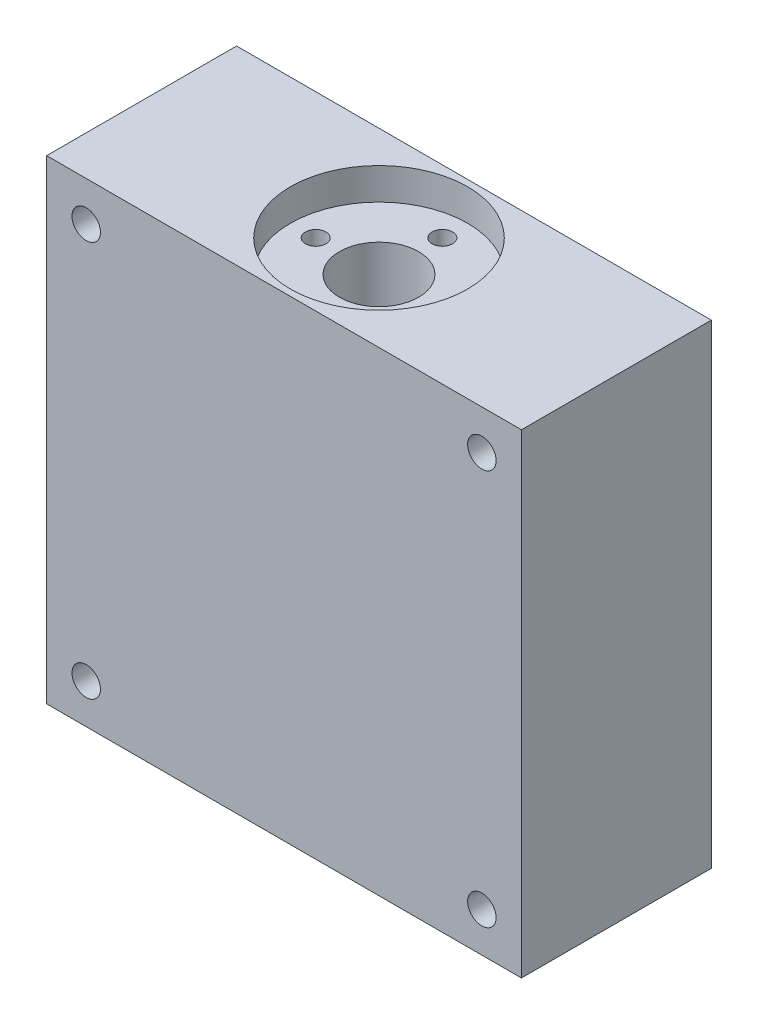
SolidWorks part; units mm, degrees
ref_plane "Front Plane" through (0, 0, 0) normal (0, 0, 1) x (1, 0, 0)
ref_plane "Top Plane" through (0, 0, 0) normal (0, 1, 0) x (1, 0, 0)
ref_plane "Right Plane" through (0, 0, 0) normal (1, 0, 0) x (0, 0, -1)
sketch "Sketch1" plane through (0, 0, 0) normal (0, 0, 1) x (1, 0, 0)
  line L1 (-30, 30) -> (30, 30)
  line L2 (-30, 30) -> (-30, -30)
  line L3 (-30, -30) -> (30, -30)
  line L4 (30, 30) -> (30, -30)
  line L5 (-30, 30) -> (30, -30) construction
  line L6 (-30, -30) -> (30, 30) construction
  line L7 (-25, -25) -> (25, -25) construction
  line L8 (-25, -25) -> (-25, 25) construction
  line L9 (-25, 25) -> (25, 25) construction
  line L10 (25, -25) -> (25, 25) construction
  line L11 (-25, -25) -> (25, 25) construction
  line L12 (-25, 25) -> (25, -25) construction
  circle A0 centre (-25, 25) radius 1.8
  circle A1 centre (25, 25) radius 1.8
  circle A2 centre (25, -25) radius 1.8
  circle A3 centre (-25, -25) radius 1.8
  point P0 (0, 0)
  point P6 (0, 0)
  dimension "D1" = 60
  dimension "D2" = 60
  dimension "D3" = 50
  dimension "D4" = 50
extrude "Boss-Extrude1" add sketch "Sketch1" along normal blind 24
sketch "Sketch2" plane through (0, 30, 0) normal (0, 1, 0) x (1, 0, 0)
  line L0 (30, 0) -> (-30, 0) construction
  circle A0 centre (0, -12) radius 11.2
  dimension "D1" = 12
extrude "Cut-Extrude1" cut sketch "Sketch2" against normal blind 4
sketch "Sketch3" plane through (0, 26, 0) normal (0, 1, 0) x (1, 0, 0)
  circle A0 centre (0, -12) radius 5
extrude "Cut-Extrude2" cut sketch "Sketch3" against normal up to next
sketch "Sketch4" plane through (0, -30, 0) normal (0, -1, 0) x (1, 0, 0)
  circle A0 centre (0, 12) radius 7.2
extrude "Cut-Extrude3" cut sketch "Sketch4" against normal blind 46
sketch "Sketch5" plane through (0, 26, 0) normal (0, 1, 0) x (1, 0, 0)
  circle A0 centre (0, -12) radius 8 construction
  circle A1 centre (0, -4) radius 1.3
  circle A2 centre (8, -12) radius 1.3
  circle A3 centre (0, -20) radius 1.3
  circle A4 centre (-8, -12) radius 1.3
extrude "Cut-Extrude4" cut sketch "Sketch5" against normal blind 6
